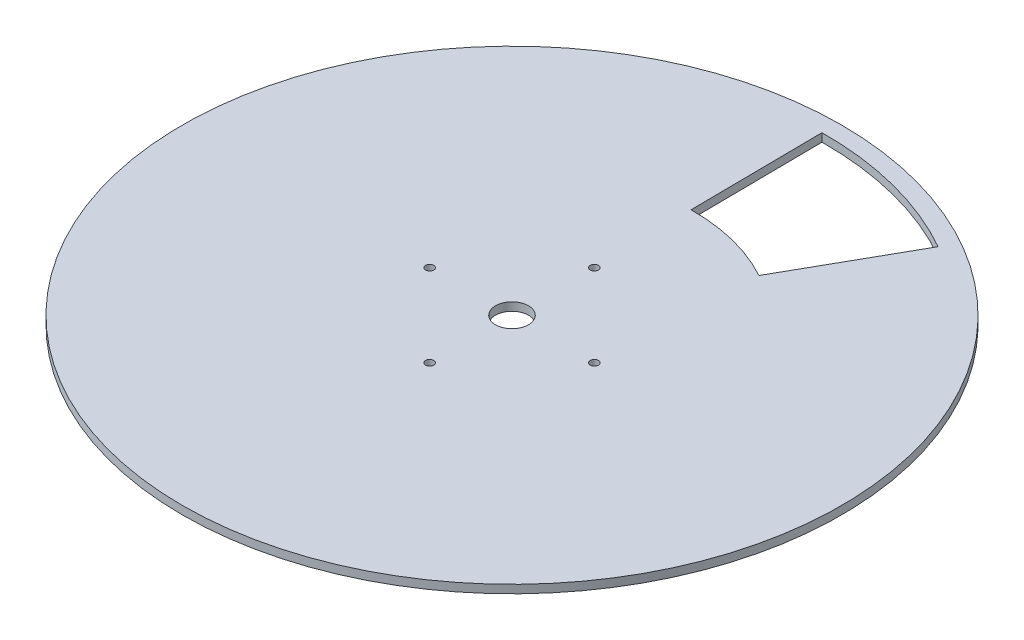
SolidWorks part; units mm, degrees
ref_plane "Front Plane" through (0, 0, 0) normal (0, 0, 1) x (1, 0, 0)
ref_plane "Top Plane" through (0, 0, 0) normal (0, 1, 0) x (1, 0, 0)
ref_plane "Right Plane" through (0, 0, 0) normal (1, 0, 0) x (0, 0, -1)
sketch "Sketch1" plane through (0, 0, 0) normal (0, 1, 0) x (1, 0, 0)
  circle A0 centre (0, 0) radius 127
  dimension "D1" = 254
extrude "Boss-Extrude1" add sketch "Sketch1" along normal blind 3.175
sketch "Sketch2" plane through (0, 3.175, 0) normal (0, 1, 0) x (1, 0, 0)
  circle A0 centre (0, 0) radius 6.35
  dimension "D1" = 12.7
extrude "Cut-Extrude1" cut sketch "Sketch2" against normal through all
sketch "Sketch3" plane through (0, 3.175, 0) normal (0, 1, 0) x (1, 0, 0)
  line L0 (0, 0) -> (-1.2681, 126.9937) construction
  line L1 (0, 0) -> (62.3986, 110.6138) construction
  line L2 (-0.6961, 69.7076) -> (-1.2047, 120.644)
  line L3 (34.3192, 60.8376) -> (59.2211, 104.981)
  circle A0 centre (0, 0) radius 69.85 construction
  circle A1 centre (0, 0) radius 120.65 construction
  circle A2 centre (0, 0) radius 127 construction
  arc A3 (-1.2047, 120.644) -> (59.2211, 104.981) centre (-0.0087, 0.869) cw
  arc A4 (-0.6961, 69.7076) -> (34.3192, 60.8376) centre (0.0105, -1.0515) cw
  dimension "D1" = 139.7
  dimension "D2" = 241.3
  dimension "D3" = 30
extrude "Cut-Extrude2" cut sketch "Sketch3" against normal through all
sketch "Sketch4" plane through (0, 3.175, 0) normal (0, 1, 0) x (1, 0, 0)
  line L0 (0, -31.75) -> (0, 0) construction
  circle A0 centre (0, -31.75) radius 1.5875
  dimension "D1" = 3.175
  dimension "D2" = 31.75
extrude "Cut-Extrude3" cut sketch "Sketch4" against normal through all
pattern_circular "CirPattern1" count 4 over 360 about axis through (0, 0, 0) along (0, 1, 0) of "Cut-Extrude3"
